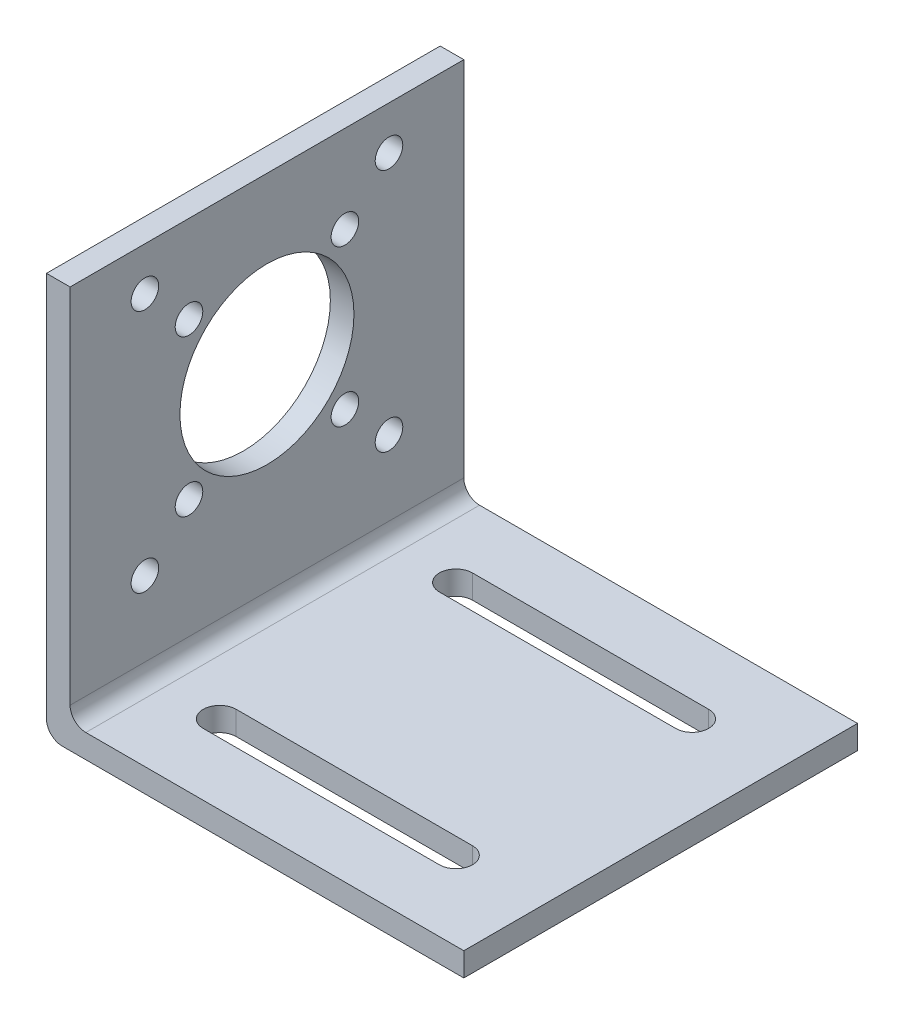
SolidWorks part; units mm, degrees
material "1060 Alloy"
ref_plane "Front" through (0, 0, 0) normal (0, 0, 1) x (1, 0, 0)
ref_plane "Top" through (0, 0, 0) normal (0, 1, 0) x (1, 0, 0)
ref_plane "Right" through (0, 0, 0) normal (1, 0, 0) x (0, 0, -1)
sketch "Sketch1" plane through (0, 0, 0) normal (0, 1, 0) x (1, 0, 0)
  line L1 (0, 0) -> (53, 0)
  line L2 (0, 0) -> (0, 50)
  line L3 (0, 50) -> (53, 50)
  line L4 (53, 0) -> (53, 50)
  dimension "D1" = 50
  dimension "D2" = 53
extrude "Boss-Extrude1" add sketch "Sketch1" along normal blind 3
sketch "Sketch2" plane through (0, 3, 0) normal (0, 1, 0) x (1, 0, 0)
  line L0 (53, 50) -> (0, 50) construction
  line L1 (0, 0) -> (3, 0)
  line L2 (0, 0) -> (0, 50)
  line L3 (0, 50) -> (3, 50)
  line L4 (3, 0) -> (3, 50)
  dimension "D1" = 3
extrude "Boss-Extrude2" add sketch "Sketch2" along normal blind 48
sketch "Sketch3" plane through (0, 3, 0) normal (0, 1, 0) x (1, 0, 0)
  line L0 (53, 0) -> (53, 50) construction
  line L1 (53, 0) -> (53, 50)
  line L2 (3, 0) -> (3, 50) construction
  line L3 (3, 0) -> (3, 50)
  line L4 (3, 25) -> (53, 25) construction
  line L5 (12, 40) -> (42, 40) construction
  line L6 (12, 42.1) -> (42, 42.1)
  line L7 (12, 37.9) -> (42, 37.9)
  line L8 (12, 10) -> (42, 10) construction
  line L9 (12, 7.9) -> (42, 7.9)
  line L10 (12, 12.1) -> (42, 12.1)
  arc A0 (12, 42.1) -> (12, 37.9) centre (12, 40) ccw
  arc A1 (42, 37.9) -> (42, 42.1) centre (42, 40) ccw
  arc A2 (12, 7.9) -> (12, 12.1) centre (12, 10) cw
  arc A3 (42, 12.1) -> (42, 7.9) centre (42, 10) cw
  point P8 (27, 40)
  point P15 (27, 10)
  dimension "D4" = 2.1
  dimension "D1" = 11
  dimension "D2" = 30
  dimension "D3" = 15
extrude "Cut-Extrude1" cut sketch "Sketch3" against normal through all contours L7 A1 L6 A0 | A3 L10 A2 L9 region at (27, 3, -40) region at (27, 3, -10)
fillet "Fillet1" radius 2 2 edges at (3, 3, -25) (0, 0, -25)
sketch "Sketch4" plane through (3, 0, 0) normal (1, 0, 0) x (0, 0, -1)
  line L0 (0, 51) -> (0, 5) construction
  line L1 (0, 51) -> (0, 5)
  line L2 (0, 0) -> (50, 0) construction
  line L3 (0, 0) -> (50, 0)
  line L4 (25, 0) -> (25, 51) construction
  line L5 (0, 51) -> (50, 51) construction
  line L6 (25, 30) -> (50, 30) construction
  line L7 (50, 51) -> (50, 5) construction
  line L9 (9.5, 14.5) -> (40.5, 14.5) construction
  line L10 (9.5, 14.5) -> (9.5, 45.5) construction
  line L11 (9.5, 45.5) -> (40.5, 45.5) construction
  line L12 (40.5, 14.5) -> (40.5, 45.5) construction
  line L13 (9.5, 14.5) -> (40.5, 45.5) construction
  line L14 (9.5, 45.5) -> (40.5, 14.5) construction
  circle A0 centre (25, 30) radius 11.05
  circle A1 centre (25, 30) radius 14 construction
  circle A2 centre (34.899, 39.9) radius 1.75
  circle A6 centre (15.101, 39.9) radius 1.75
  circle A7 centre (15.101, 20.1) radius 1.75
  circle A8 centre (34.899, 20.1) radius 1.75
  circle A9 centre (9.5, 45.5) radius 1.75
  circle A10 centre (40.5, 45.5) radius 1.75
  circle A11 centre (9.5, 14.5) radius 1.75
  circle A12 centre (40.5, 14.5) radius 1.75
  dimension "D1" = 22.1
  dimension "D3" = 28
  dimension "D4" = 3.5
  dimension "D2" = 30
  dimension "D5" = 9.9
  dimension "D6" = 9.9
  dimension "D7" = 31
extrude "Cut-Extrude2" cut sketch "Sketch4" against normal through all contours A9 | A6 | A0 | A7 | A11 | A8 | A12 | A2 | A10 | A12 region at (3, 30, -25) region at (3, 39.9, -34.899) region at (3, 39.9, -15.101) region at (3, 20.1, -15.101) region at (3, 20.1, -34.899) region at (3, 45.5, -9.5) region at (3, 45.5, -40.5) region at (3, 14.5, -9.5) region at (3, 14.5, -40.5)
